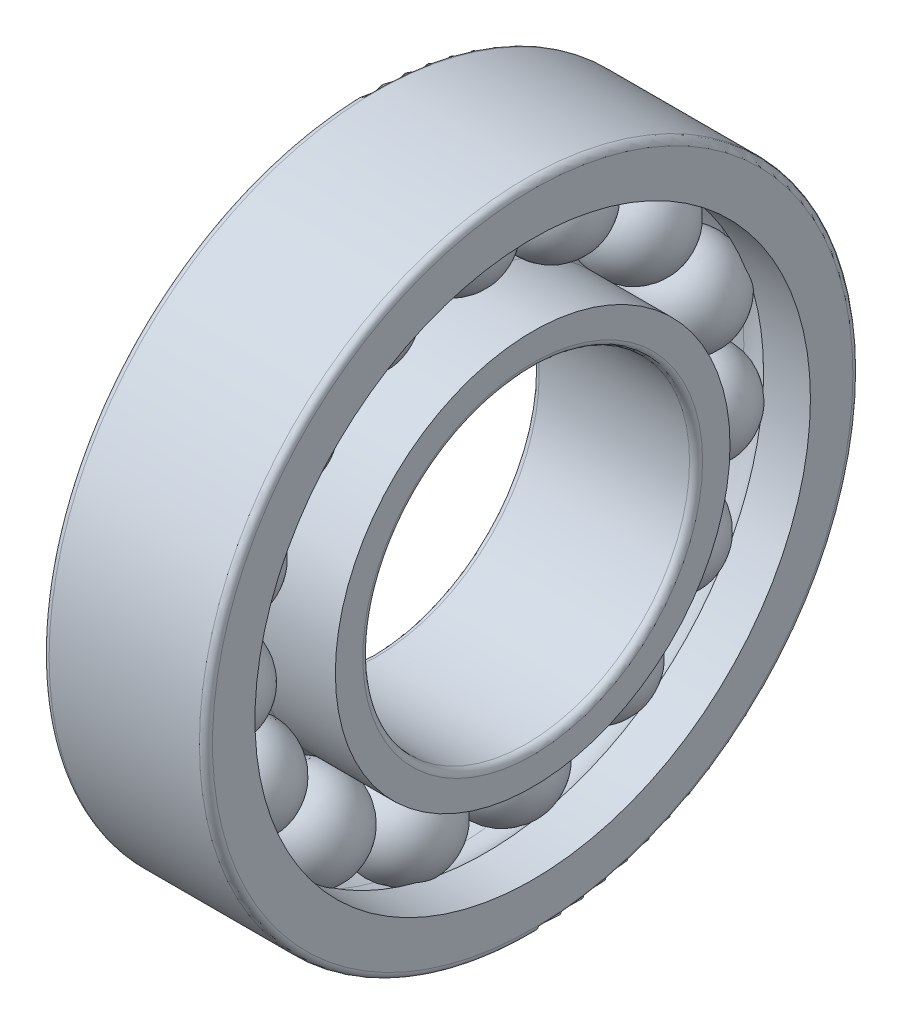
SolidWorks part; units mm, degrees
ref_plane "Plane1" through (0, 0, 0) normal (0, 0, 1) x (1, 0, 0)
ref_plane "Plane2" through (0, 0, 0) normal (0, 1, 0) x (1, 0, 0)
ref_plane "Plane3" through (0, 0, 0) normal (1, 0, 0) x (0, 0, -1)
sketch "Clipboard" plane through (0, 0, 0) normal (0, 0, 1) x (1, 0, 0)
  line L0 (-10, 0) -> (10, 0) construction
  line L1 (0, 0) -> (21.5988, -5.7874)
  line L2 (0, 0) -> (4.7618, -0.0831)
  line L3 (0, 0) -> (22.3573, 0.3902)
  line L4 (0, 0) -> (-22.3573, -0.3902)
  dimension "BallCLRad" = 4.7625
sketch "CagSpiSke" plane through (0, 0, 0) normal (0, 0, 1) x (1, 0, 0)
  line L0 (0.2381, 4.6037) -> (0.2381, 4.9213)
  line L1 (0.2381, 4.9213) -> (-0.2381, 4.9213)
  line L2 (-0.2381, 4.9213) -> (-0.2381, 4.6037)
  line L3 (-0.2381, 4.6037) -> (0.2381, 4.6037)
  line L4 (-20.6375, 0) -> (20.6375, 0) construction
  line L5 (0, 0) -> (0, 23.7692) construction
  dimension "OD" = 9.8425
  dimension "ID" = 9.2075
revolve "CageSpine" add sketch "CagSpiSke" angle 0.001 about L4
ref_axis "Axis1" through (-50, 0, 0) along (1, 0, 0)
sketch "CagBalSke" plane through (0, 0, 0) normal (0, 0, 1) x (1, 0, 0)
  line L0 (-1.0478, 4.7625) -> (1.0478, 4.7625)
  line L1 (-1.905, 4.7625) -> (1.905, 4.7625) construction
  line L2 (-10, 0) -> (10, 0) construction
  line L3 (0, 0) -> (0, 24) construction
  arc A0 (1.0478, 4.7625) -> (-1.0478, 4.7625) centre (0, 4.7625) cw
  dimension "BallCLRad" = 4.7625
revolve "CageBall" [suppressed] add sketch "CagBalSke" angle 360 about L1 reverse direction yes
pattern_circular "CageBalls" [suppressed] count 15 every 24 about axis through (-50, 0, 0) along (1, 0, 0)
sketch "CagTrmODSke" plane through (0, 0, 0) normal (0, 0, 1) x (1, 0, 0)
  line L0 (1.0488, 4.9212) -> (1.0488, 5.8113)
  line L1 (1.0488, 5.8113) -> (-1.0488, 5.8113)
  line L2 (-1.0488, 5.8113) -> (-1.0488, 4.9212)
  line L3 (-1.0488, 4.9212) -> (1.0488, 4.9212)
  line L4 (-20.6375, 0) -> (20.6375, 0) construction
  line L5 (0, 0) -> (0, 25) construction
  dimension "Width" = 2.0975
  dimension "ID" = 9.8425
  dimension "OD" = 11.6225
revolve "CageTrimOD" [suppressed] cut sketch "CagTrmODSke" angle 360 about L4 reverse direction yes
sketch "CagTrmIDSke" plane through (0, 0, 0) normal (0, 0, 1) x (1, 0, 0)
  line L0 (1.0487, 3.7158) -> (1.0488, 4.6037)
  line L1 (1.0488, 4.6037) -> (-1.0488, 4.6037)
  line L2 (-1.0488, 4.6037) -> (-1.0487, 3.7158)
  line L3 (-1.0487, 3.7158) -> (1.0487, 3.7158)
  line L4 (-20.6375, 0) -> (20.6375, 0) construction
  line L5 (0, 0) -> (0, 25) construction
  dimension "Width" = 2.0975
  dimension "ID" = 7.4315
  dimension "OD" = 9.2075
revolve "CageTrimID" [suppressed] cut sketch "CagTrmIDSke" angle 360 about L4 reverse direction yes
sketch "BalSimSke" plane through (0, 0, 0) normal (0, 0, 1) x (1, 0, 0)
  line L0 (-10, 0) -> (10, 0) construction
  line L1 (-10, 4.7625) -> (10, 4.7625) construction
  line L2 (0, 0) -> (0, 23) construction
  circle A0 centre (0, 4.7625) radius 0.9525
  dimension "BallCLRad" = 4.7625
  dimension "Ball_diameter" = 1.905
revolve "BallsSimplified" [suppressed] add sketch "BalSimSke" angle 360 about L0
sketch "BalDetSke" plane through (0, 0, 0) normal (0, 0, 1) x (1, 0, 0)
  line L0 (-0.9525, 4.7625) -> (0.9525, 4.7625)
  line L1 (-1.905, 4.7625) -> (1.905, 4.7625) construction
  line L2 (0, 0) -> (0, 25) construction
  arc A0 (0.9525, 4.7625) -> (-0.9525, 4.7625) centre (0, 4.7625) cw
  dimension "BallCLRad" = 4.7625
  dimension "Ball_diameter" = 1.905
revolve "BallDetailed" add sketch "BalDetSke" angle 360 about L1 reverse direction yes
sketch "InnRacSke" plane through (0, 0, 0) normal (0, 0, 1) x (1, 0, 0)
  line L0 (-0.676, 4.1275) -> (-1.5875, 4.1275)
  line L1 (-1.5875, 4.1275) -> (-1.5875, 3.302)
  line L2 (-1.4605, 3.175) -> (1.4605, 3.175)
  line L3 (1.5875, 3.302) -> (1.5875, 3.835)
  line L4 (0, 3.835) -> (1.5875, 3.835)
  line L5 (-20.6375, 0) -> (20.6375, 0) construction
  line L6 (0, 0) -> (0, 30) construction
  arc A0 (-1.5875, 3.302) -> (-1.4605, 3.175) centre (-1.4605, 3.302) ccw
  arc A1 (1.4605, 3.175) -> (1.5875, 3.302) centre (1.4605, 3.302) ccw
  arc A2 (0, 3.835) -> (-0.676, 4.1275) centre (0, 4.7625) cw
  dimension "BallCLRad" = 4.7625
  dimension "Fillet_radius" = 0.127
  dimension "Ball_diameter" = 1.855
  dimension "ID" = 6.35
  dimension "OD" = 8.255
  dimension "Width" = 3.175
revolve "InnerRace" add sketch "InnRacSke" angle 360 about L5 reverse direction yes
sketch "OutRacSke" plane through (0, 0, 0) normal (0, 0, 1) x (1, 0, 0)
  line L0 (0, 5.69) -> (-1.5875, 5.69)
  line L1 (-1.5875, 5.69) -> (-1.5875, 6.223)
  line L2 (-1.4605, 6.35) -> (1.4605, 6.35)
  line L3 (1.5875, 6.223) -> (1.5875, 5.3975)
  line L4 (1.5875, 5.3975) -> (0.676, 5.3975)
  line L5 (-20.6375, 0) -> (20.6375, 0) construction
  line L6 (0, 0) -> (0, 30) construction
  arc A0 (-1.5875, 6.223) -> (-1.4605, 6.35) centre (-1.4605, 6.223) cw
  arc A1 (1.4605, 6.35) -> (1.5875, 6.223) centre (1.4605, 6.223) cw
  arc A2 (0.676, 5.3975) -> (0, 5.69) centre (0, 4.7625) ccw
  dimension "BallCLRad" = 4.7625
  dimension "Fillet_radius" = 0.127
  dimension "Ball_diameter" = 1.855
  dimension "Width" = 3.175
revolve "OuterRace" add sketch "OutRacSke" angle 360 about L5 reverse direction yes
pattern_circular "BallsDetailed" count 15 every 24 about axis through (-50, 0, 0) along (1, 0, 0) of "BallDetailed"
equation "\"BallCLRad@Clipboard\" = ( \"OD@OutRacSke\" + \"ID@InnRacSke\" ) / 4"
equation "\"BallCLRad@BalSimSke\" = \"BallCLRad@Clipboard\""
equation "\"BallCLRad@BalDetSke\" = \"BallCLRad@Clipboard\""
equation "\"BallCLRad@InnRacSke\" = \"BallCLRad@Clipboard\""
equation "\"BallCLRad@OutRacSke\" = \"BallCLRad@Clipboard\""
equation "\"Ball_diameter@InnRacSke\" = \"Ball_diameter@BalDetSke\" - 0.05"
equation "\"Ball_diameter@OutRacSke\" = \"Ball_diameter@BalDetSke\" - 0.05"
equation "\"Ball_diameter@BalSimSke\" = \"Ball_diameter@BalDetSke\""
equation "\"Width@OutRacSke\" = \"Width@InnRacSke\""
equation "\"Fillet_radius@OutRacSke\" = \"Fillet_radius@InnRacSke\""
equation "\"Max_count@Clipboard\" = int( 3.14159265 / atn(( \"Ball_diameter@BalDetSke\" / 2) / sqr( \"BallCLRad@Clipboard\"  *  \"BallCLRad@Clipboard\" - ( \"Ball_diameter@BalDetSke\" / 2) *  ( \"Ball_diameter@BalDetSke\" / 2))))"
equation "\"Max_count@Clipboard\" = ((sgn( \"Max_count@Clipboard\" - \"Count@Clipboard\" )-1)*( \"Max_count@Clipboard\" - \"Count@Clipboard\" ))/-2+ \"Count@Clipboard\""
equation "\"Count@BallsDetailed\" = int( \"Show_count@Clipboard\" ) "
equation "\"Count@BallsDetailed\" = ((sgn( \"Count@BallsDetailed\" - \"Max_count@Clipboard\" )-1)*( \"Count@BallsDetailed\" - \"Max_count@Clipboard\" ))/-2+ \"Max_count@Clipboard\""
equation "\"Count@BallsDetailed\" = ((sgn( \"Count@BallsDetailed\" - \"Min_count@Clipboard\" )+1)*( \"Count@BallsDetailed\" - \"Min_count@Clipboard\"))/2 +\"Min_count@Clipboard\""
equation "\"Angle@BallsDetailed\" = 360.0 / \"Max_count@Clipboard\""
equation "\"BallCLRad@CagBalSke\" = \"BallCLRad@Clipboard\""
equation "\"Count@CageBalls\" = \"Count@BallsDetailed\""
equation "\"Angle@CageBalls\" = \"Angle@BallsDetailed\""
equation "\"Angle@CageSpine\" =  \"Angle@CageBalls\" * ( \"Count@CageBalls\" -1 + int( \"Count@CageBalls\" / \"Max_count@Clipboard\" ) )  + 0.001 -  int( \"Count@CageBalls\" / \"Max_count@Clipboard\" ) * 0.001"
equation "\"Angle@CageSpine\" =  \"Angle@CageSpine\" * int( \"Min_count@Clipboard\" / 2) + int(1 / \"Min_count@Clipboard\")  * 0.001"
equation "\"CageWallOD@CagBalSke\" =  \"Ball_diameter@BalDetSke\" * 1.1"
equation "\"Thickness@CagSpiSke\" =  \"Ball_diameter@BalDetSke\" * 0.25"
equation "\"OD@CagTrmODSke\" = \"BallCLRad@Clipboard\" * 2 + \"CageWallOD@CagBalSke\" + 0.002"
equation "\"ID@CagTrmODSke\" = \"BallCLRad@Clipboard\" * 2 + \"Ball_diameter@BalDetSke\" / 6"
equation "\"OD@CagTrmIDSke\" = \"BallCLRad@Clipboard\" * 2 - \"Ball_diameter@BalDetSke\" / 6"
equation "\"ID@CagTrmIDSke\" = \"BallCLRad@Clipboard\" * 2 - \"CageWallOD@CagBalSke\" + 0.002"
equation "\"OD@CagSpiSke\" = \"ID@CagTrmODSke\""
equation "\"ID@CagSpiSke\" = \"OD@CagTrmIDSke\""
equation "\"Width@CagTrmODSke\" = \"CageWallOD@CagBalSke\" + 0.002"
equation "\"Width@CagTrmIDSke\" = \"CageWallOD@CagBalSke\" + 0.002"
